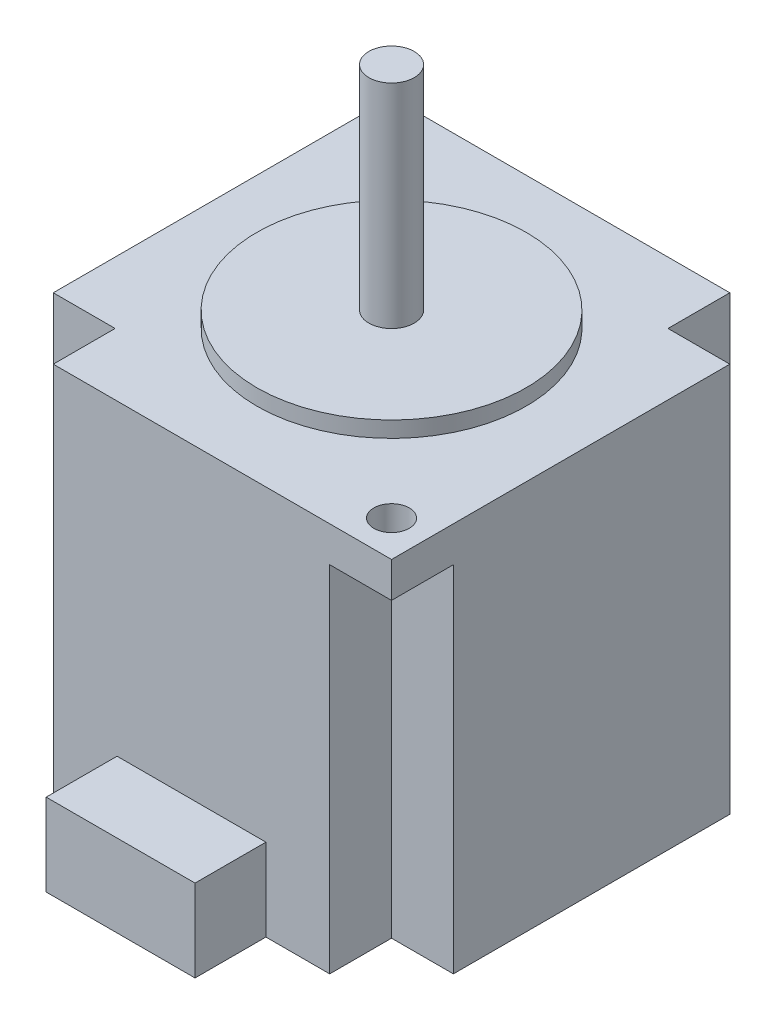
SolidWorks part; units mm, degrees
ref_plane "Front Plane" through (0, 0, 0) normal (0, 0, 1) x (1, 0, 0)
ref_plane "Top Plane" through (0, 0, 0) normal (0, 1, 0) x (1, 0, 0)
ref_plane "Right Plane" through (0, 0, 0) normal (1, 0, 0) x (0, 0, -1)
sketch "Sketch1" plane through (0, 0, 0) normal (0, 1, 0) x (1, 0, 0)
  line L1 (-28.225, 28.225) -> (28.225, 28.225)
  line L2 (-28.225, 28.225) -> (-28.225, -28.225)
  line L3 (-28.225, -28.225) -> (28.225, -28.225)
  line L4 (28.225, 28.225) -> (28.225, -28.225)
  line L5 (-28.225, 28.225) -> (28.225, -28.225) construction
  line L6 (-28.225, -28.225) -> (28.225, 28.225) construction
  point P0 (0, 0)
  dimension "D1" = 56.45
extrude "Boss-Extrude1" add sketch "Sketch1" along normal blind 55
sketch "Sketch2" plane through (0, 55, 0) normal (0, 1, 0) x (1, 0, 0)
  circle A0 centre (0, 0) radius 19
  dimension "D1" = 38
extrude "Boss-Extrude2" add sketch "Sketch2" along normal blind 2.25
sketch "Sketch3" plane through (0, 57.25, 0) normal (0, 1, 0) x (1, 0, 0)
  circle A0 centre (0, 0) radius 3.2
  dimension "D1" = 6.4
extrude "Boss-Extrude3" add sketch "Sketch3" along normal blind 30
sketch "Sketch4" plane through (0, 0, 0) normal (0, -1, 0) x (1, 0, 0)
  line L0 (0, 28.225) -> (19.5, 28.225)
  line L1 (-28.225, 28.225) -> (28.225, 28.225) construction
  line L2 (0, 28.225) -> (-19.5, 28.225)
  line L3 (-28.225, 0) -> (-28.225, 19.5)
  line L4 (-28.225, -28.225) -> (-28.225, 28.225) construction
  line L5 (-28.225, 0) -> (-28.225, -19.5)
  line L6 (28.225, 0) -> (28.225, 19.5)
  line L7 (28.225, 28.225) -> (28.225, -28.225) construction
  line L8 (28.225, 0) -> (28.225, -19.5)
  line L9 (0, -28.225) -> (19.5, -28.225)
  line L10 (28.225, -28.225) -> (-28.225, -28.225) construction
  line L11 (0, -28.225) -> (-19.5, -28.225)
  line L12 (19.5, 28.225) -> (28.225, 28.225)
  line L13 (28.225, 28.225) -> (28.225, 19.5)
  line L14 (28.225, 19.5) -> (19.5, 19.5)
  line L15 (19.5, 19.5) -> (19.5, 28.225)
  line L16 (28.225, -19.5) -> (28.225, -28.225)
  line L17 (28.225, -28.225) -> (19.5, -28.225)
  line L18 (19.5, -28.225) -> (19.5, -19.5)
  line L19 (19.5, -19.5) -> (28.225, -19.5)
  line L20 (-19.5, -28.225) -> (-28.225, -28.225)
  line L21 (-28.225, -28.225) -> (-28.225, -19.5)
  line L22 (-28.225, -19.5) -> (-19.5, -19.5)
  line L23 (-19.5, -19.5) -> (-19.5, -28.225)
  line L24 (-28.225, 19.5) -> (-28.225, 28.225)
  line L25 (-28.225, 28.225) -> (-19.5, 28.225)
  line L26 (-19.5, 19.5) -> (-19.5, 28.225)
  line L27 (-19.5, 19.5) -> (-28.225, 19.5)
  dimension "D1" = 19.5
  dimension "D2" = 19.5
  dimension "D3" = 19.5
  dimension "D4" = 19.5
  dimension "D5" = 19.5
  dimension "D6" = 19.5
  dimension "D7" = 19.5
  dimension "D8" = 19.5
extrude "Cut-Extrude1" cut sketch "Sketch4" against normal up to surface (55 mm away) contours L26 L27 L24 L25 | L18 L19 L16 L17 up to face at (0, 55, 19)
extrude "Cut-Extrude2" cut sketch "Sketch4<3>" against normal blind 50 contours L14 L15 L12 L13 | L23 L22 L21 L20
sketch "Sketch4<3>" plane through (0, 0, 0) normal (0, -1, 0) x (1, 0, 0) same geometry as "Sketch4"
sketch "Sketch5" plane through (0, 0, 0) normal (0, -1, 0) x (1, 0, 0)
  line L0 (0, 28.225) -> (10.5, 28.225)
  line L1 (-19.5, 28.225) -> (19.5, 28.225) construction
  line L2 (0, 28.225) -> (-10.5, 28.225)
  line L3 (-10.5, 28.225) -> (-10.5, 38.225)
  line L4 (-10.5, 38.225) -> (10.5, 38.225)
  line L5 (10.5, 38.225) -> (10.5, 28.225)
  dimension "D1" = 10.5
  dimension "D2" = 10.5
  dimension "D3" = 10
extrude "Boss-Extrude4" add sketch "Sketch5" against normal blind 11.6
sketch "Sketch6" plane through (0, 55, 0) normal (0, 1, 0) x (1, 0, 0)
  line L0 (28.225, -28.225) -> (28.225, 19.5) construction
  line L1 (-19.5, -28.225) -> (28.225, -28.225) construction
  line L2 (19.5, 28.225) -> (-28.225, 28.225) construction
  line L3 (-28.225, 28.225) -> (-28.225, -19.5) construction
  circle A0 centre (-23.175, 23.175) radius 2.5
  circle A1 centre (23.175, -23.175) radius 2.5
  dimension "D1" = 5
  dimension "D2" = 2.5
  dimension "D3" = 5.05
  dimension "D4" = 5.05
  dimension "D5" = 5.05
  dimension "D6" = 5.05
extrude "Cut-Extrude3" cut sketch "Sketch6" against normal up to surface (5 mm away) up to face at (-23.8625, 50, -23.8625)
sketch "Sketch7" plane through (0, 0, 0) normal (0, -1, 0) x (1, 0, 0)
  circle A0 centre (0, 0) radius 4.5
  dimension "D1" = 9
extrude "Cut-Extrude4" cut sketch "Sketch7" against normal blind 2.35
